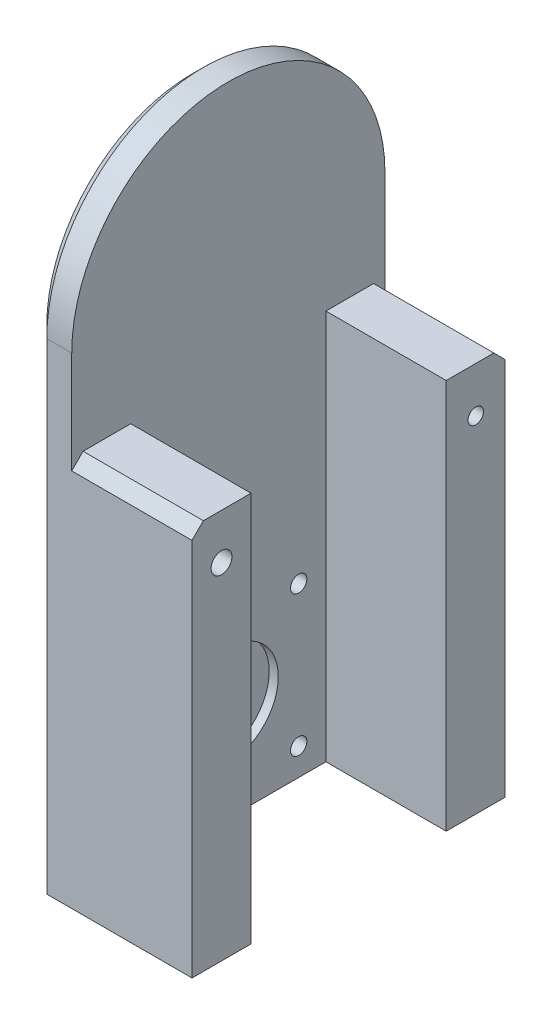
SolidWorks part; units mm, degrees
ref_plane "Ebene vorne" through (0, 0, 0) normal (0, 0, 1) x (1, 0, 0)
ref_plane "Ebene oben" through (0, 0, 0) normal (0, 1, 0) x (1, 0, 0)
ref_plane "Ebene rechts" through (0, 0, 0) normal (1, 0, 0) x (0, 0, -1)
sketch "Sketch2" plane through (0, 0, 0) normal (1, 0, 0) x (0, 0, -1)
  line L1 (0, 0) -> (69, 0)
  line L2 (0, 0) -> (0, 86)
  line L3 (0, 86) -> (69, 86)
  line L4 (69, 0) -> (69, 86)
  line L5 (0, 0) -> (69, 86) construction
  line L6 (0, 86) -> (69, 0) construction
  line L7 (0, 86) -> (69, 86)
  line L8 (0, 86) -> (0, 106)
  line L9 (0, 106) -> (69, 106)
  line L10 (69, 86) -> (69, 106)
  line L11 (0, 86) -> (69, 106) construction
  line L12 (0, 106) -> (69, 86) construction
  circle A0 centre (34.5, 106) radius 34.5
  point P4 (34.5, 43)
  point P9 (34.5, 96)
  dimension "D4" = 69
  dimension "D1" = 69
  dimension "D2" = 86
  dimension "D3" = 20
extrude "Boss-Extrude1" add sketch "Sketch2" along normal blind 34.5 contours A0 L3 L2 L1 L4 | L7 A0 region at (0, 39.049, -34.5) region at (0, 80.0809, -34.5)
sketch "Sketch3" plane through (34.5, 0, 0) normal (1, 0, 0) x (0, 0, -1)
  line L0 (13, 86) -> (13, 0)
  line L1 (0, 86) -> (69, 86) construction
  line L2 (0, 0) -> (69, 0) construction
  line L3 (13, 0) -> (56, 0)
  line L4 (56, 0) -> (56, 86)
  line L5 (56, 86) -> (13, 86)
  line L6 (0, 0) -> (0, 86) construction
  line L7 (69, 0) -> (69, 86) construction
  line L9 (13, 0) -> (56, 0)
  line L10 (13, 0) -> (13, 43)
  line L11 (13, 43) -> (56, 43)
  line L12 (56, 0) -> (56, 43)
  line L13 (13, 0) -> (56, 43) construction
  line L14 (13, 43) -> (56, 0) construction
  line L15 (56, 43) -> (13, 43)
  line L16 (56, 43) -> (56, 86)
  line L17 (56, 86) -> (13, 86)
  line L18 (13, 43) -> (13, 86)
  line L19 (56, 43) -> (13, 86) construction
  line L20 (56, 86) -> (13, 43) construction
  circle A0 centre (34.5, 21.5) radius 11
  circle A1 centre (34.5, 21.5) radius 3.5
  point P15 (34.5, 21.5)
  point P19 (34.5, 64.5)
  line M14 (69, 86) -> (0, 86)
  line M16 (0, 0) -> (69, 0)
  dimension "D3" = 22
  dimension "D4" = 7
  dimension "D1" = 13
  dimension "D2" = 13
extrude "Cut-Extrude1" cut sketch "Sketch3" against normal offset from surface (26.5 mm away) 8 contours L0 L11 L4 M14 | A0 A1 | A1 | L11 L0 L4 A0 M16 region at (34.5, 64.5, -34.5) region at (34.5, 42.3919, -34.5) region at (34.5, 21.5, -23.8111) region at (34.5, 21.5, -34.5) up to face at (0, 43, -34.5)
extrude "Boss-Extrude2" add sketch "Sketch2<3>" along normal up to surface (8 mm away) contours L9 A0 L7 | A0 L3 L10 | A0 L8 L3 | L9 A0 region at (0, 90.9027, -1.8818) region at (0, 90.9027, -67.1182) region at (0, 96.321, -34.5) region at (0, 120.6423, -34.5) up to face at (8, 43, -34.5)
sketch "Sketch2<3>" plane through (0, 0, 0) normal (1, 0, 0) x (0, 0, -1) same geometry as "Sketch2"
extrude "Cut-Extrude2" cut sketch "Sketch3<3>" against normal offset from surface (28.5 mm away) 2 contours A0 A1 | A1 region at (34.5, 21.5, -23.8111) region at (34.5, 21.5, -34.5) up to face at (8, 73.8125, -34.5) offset beyond the face yes
sketch "Sketch3<3>" plane through (34.5, 0, 0) normal (1, 0, 0) x (0, 0, -1) same geometry as "Sketch3"
extrude "Cut-Extrude3" cut sketch "Sketch3<4>" against normal through all contours A1 region at (34.5, 21.5, -34.5)
sketch "Sketch3<4>" plane through (34.5, 0, 0) normal (1, 0, 0) x (0, 0, -1) same geometry as "Sketch3"
hole_wizard "CBORE for M3 Hex Socket Head Cap Screw1" positions "Sketch4" profile "Sketch5" counterbore size "M3" standard "DIN" end condition through all
sketch "Sketch4" plane through (0, 0, 0) normal (-1, 0, 0) x (0, 0, 1)
  line L1 (-50, 6) -> (-19, 6)
  line L2 (-50, 6) -> (-50, 37)
  line L3 (-50, 37) -> (-19, 37)
  line L4 (-19, 6) -> (-19, 37)
  line L5 (-50, 6) -> (-19, 37) construction
  line L6 (-50, 37) -> (-19, 6) construction
  point P0 (-34.5, 21.5)
  point P1 (-19, 37)
  point P4 (-50, 6)
  point P5 (-50, 37)
  point P6 (-19, 6)
  dimension "D1" = 31
sketch "Sketch5" plane through (0, 6, -19) normal (0, 1, 0) x (0, 0, 1)
  line L0 (0, 0) -> (0, 34.5)
  line L1 (0, 34.5) -> (1.8, 34.5)
  line L3 (1.8, 34.5) -> (1.8, 3.4)
  line L4 (1.8, 3.4) -> (3.25, 3.4)
  line L5 (3.25, 3.4) -> (3.25, 0)
  line L7 (3.25, 0) -> (0, 0)
  line L11 (0, -6.35) -> (0, 107.95) construction
  dimension "Thru Hole Dia." = 3.6
  dimension "Thru Hole Depth" = 34.5
  dimension "C'Bore Dia." = 6.5
  dimension "C'Bore Depth" = 3.4
hole_wizard "Ø4.6 (4.6) Diameter Hole1" positions "Sketch8" profile "Sketch9" hole size "Ø4.6" standard "DIN"
sketch "Sketch8" plane through (0, 0, 0) normal (0, -1, 0) x (-1, 0, 0)
  line L0 (-34.5, 69) -> (-34.5, 0) construction
  line L1 (-34.5, 0) -> (0, 0) construction
  line L2 (-34.5, 0) -> (-34.5, 13) construction
  line L5 (-65, 6.5) -> (-4, 6.5)
  line L6 (-65, 6.5) -> (-65, 62.5)
  line L7 (-65, 62.5) -> (-4, 62.5)
  line L8 (-4, 6.5) -> (-4, 62.5)
  line L9 (-65, 6.5) -> (-4, 62.5) construction
  line L10 (-65, 62.5) -> (-4, 6.5) construction
  line L11 (-34.5, 69) -> (0, 69) construction
  line L12 (0, 0) -> (0, 69) construction
  point P9 (-34.5, 34.5)
  point P10 (-4, 62.5)
  point P15 (-4, 6.5)
  point P89 (-4, 34.5)
  dimension "D1" = 6.5
  dimension "D2" = 4
sketch "Sketch9" plane through (4, 0, -34.5) normal (1, 0, 0) x (0, 0, -1)
  line L0 (0, 0) -> (0, 7.382)
  line L1 (0, 7.382) -> (2.3, 6)
  line L2 (2.3, 6) -> (2.3, 0)
  line L5 (2.3, 0) -> (0, 0)
  line L10 (0, 7.382) -> (-2.3, 6) construction
  line L11 (0, -6.35) -> (0, 107.95) construction
  dimension "Hole Dia." = 4.6
  dimension "Hole Depth" = 6
  dimension "Drill Angle" = 118
hole_wizard "CBORE for M3 Hex Socket Head Cap Screw2" positions "Sketch10" profile "Sketch11" counterbore size "M3" standard "DIN" end condition through all
sketch "Sketch10" plane through (0, 0, 0) normal (-1, 0, 0) x (0, 0, 1)
  line L0 (-56, 86) -> (-69, 86) construction
  line L1 (-56, 86) -> (-69, 86)
  line L2 (-62.5, 86) -> (-62.5, 76) construction
  point P4 (-62.5, 76)
  dimension "D1" = 10
sketch "Sketch11" plane through (0, 76, -62.5) normal (0, 1, 0) x (0, 0, 1)
  line L0 (0, 0) -> (0, 34.5)
  line L1 (0, 34.5) -> (1.7, 34.5)
  line L3 (1.7, 34.5) -> (1.7, 3.4)
  line L4 (1.7, 3.4) -> (3.25, 3.4)
  line L5 (3.25, 3.4) -> (3.25, 0)
  line L7 (3.25, 0) -> (0, 0)
  line L11 (0, -6.35) -> (0, 107.95) construction
  dimension "Thru Hole Dia." = 3.4
  dimension "Thru Hole Depth" = 34.5
  dimension "C'Bore Dia." = 6.5
  dimension "C'Bore Depth" = 3.4
hole_wizard "Ø4.6 (4.6) Diameter Hole2" positions "Sketch12" profile "Sketch14" hole size "Ø4.6" standard "DIN"
sketch "Sketch12" plane through (34.5, 0, 0) normal (1, 0, 0) x (0, 0, -1)
  line L0 (6.5, 86) -> (6.5, 76) construction
  line L1 (0, 86) -> (13, 86) construction
  point P1 (6.5, 76)
  dimension "D1" = 10
sketch "Sketch14" plane through (34.5, 76, -6.5) normal (0, 1, 0) x (0, 0, -1)
  line L0 (0, 0) -> (0, 7.382)
  line L1 (0, 7.382) -> (2.3, 6)
  line L2 (2.3, 6) -> (2.3, 0)
  line L5 (2.3, 0) -> (0, 0)
  line L10 (0, 7.382) -> (-2.3, 6) construction
  line L11 (0, -6.35) -> (0, 107.95) construction
  dimension "Hole Dia." = 4.6
  dimension "Hole Depth" = 6
  dimension "Drill Angle" = 118
chamfer "2,5mm Chamfer1" distance 2.5 angle 45 5 edges at (21.25, 86, -69) (21.25, 86, 0) (0, 53, 0) (0, 140.5, -34.5) (0, 53, -69)
